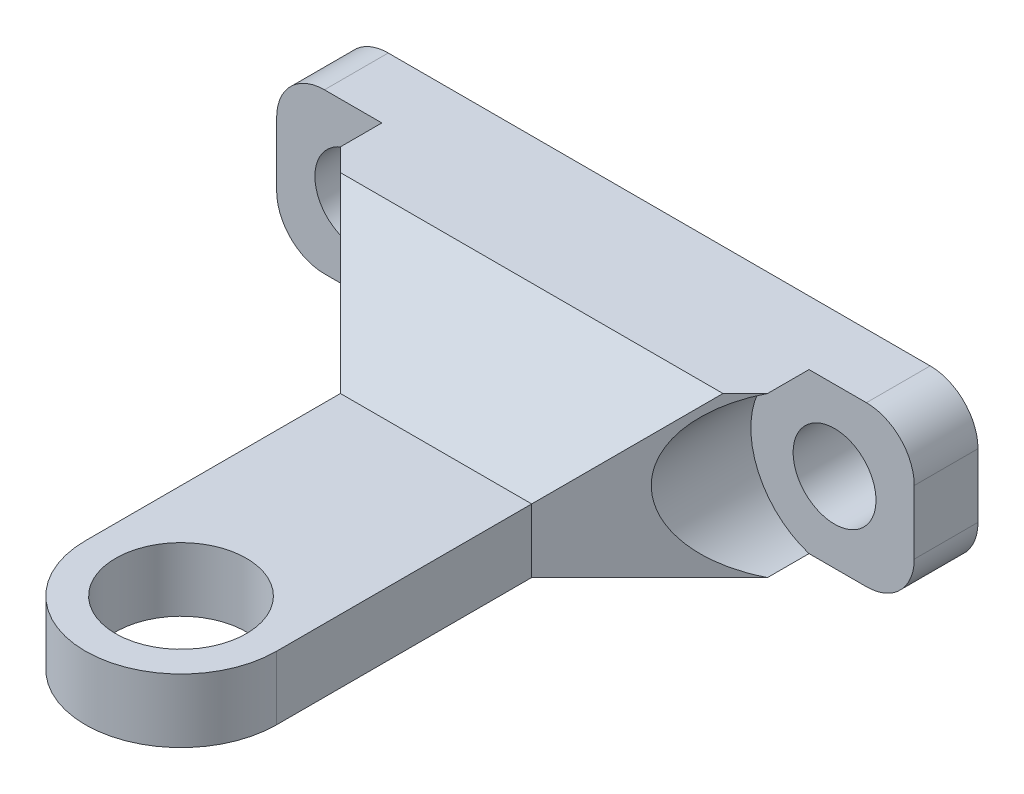
SolidWorks part; units mm, degrees
material "ABS"
ref_plane "Plano frontal" through (0, 0, 0) normal (0, 0, 1) x (1, 0, 0)
ref_plane "Plano superior" through (0, 0, 0) normal (0, 1, 0) x (1, 0, 0)
ref_plane "Plano direito" through (0, 0, 0) normal (1, 0, 0) x (0, 0, -1)
sketch "Esboço1" plane through (0, 0, 0) normal (0, 1, 0) x (1, 0, 0)
  line L0 (0, 18) -> (0, -18) construction
  line L1 (-20, 18) -> (20, 18)
  line L2 (-20, 18) -> (-20, -18)
  line L3 (-20, -18) -> (20, -18)
  line L4 (20, 18) -> (20, -18)
  line L5 (-20, 18) -> (20, -18) construction
  line L6 (-20, -18) -> (20, 18) construction
  line L7 (-6, -12) -> (-6, 14)
  line L8 (-20, 18) -> (20, 18)
  line L9 (-20, 18) -> (-20, 14)
  line L10 (-20, 14) -> (20, 14)
  line L11 (20, 18) -> (20, 14)
  line L12 (6, -12) -> (6, 14)
  circle A0 centre (0, -12) radius 6
  circle A1 centre (0, -12) radius 4.1
  point P0 (0, 0)
  dimension "D2" = 40
  dimension "D3" = 12
  dimension "D4" = 8.2
  dimension "D1" = 36
  dimension "D5" = 4
extrude "Ressalto-extrusão1" add sketch "Esboço1" along normal mid plane 4 contours L2 L10 L4 L1 | A0 L12 L10 L7 | A0 A1 region at (0, 0, -16) region at (0, 0, -3.3141) region at (-4.1226, 0, 16.1226)
sketch "Esboço2" plane through (0, 2, 0) normal (0, 1, 0) x (1, 0, 0)
  line L1 (-20, 18) -> (20, 18)
  line L2 (-20, 18) -> (-20, 14)
  line L3 (-20, 14) -> (20, 14)
  line L4 (20, 18) -> (20, 14)
extrude "Ressalto-extrusão2" add sketch "Esboço2" along normal blind 6
chamfer "Chanfro3" distance 10 angle 45 1 edges at (6, 0, -14)
chamfer "Chanfro4" distance 10 angle 45 1 edges at (-6, 0, -14)
chamfer "Chanfro5" distance 10 angle 45 1 edges at (0, 2, -14)
sketch "Esboço6" plane through (0, 0, -14) normal (0, 0, 1) x (1, 0, 0)
  line L0 (-20, 3) -> (20, 3) construction
  line L1 (-20, 8) -> (-20, -2) construction
  line L2 (20, 8) -> (20, -2) construction
  circle A0 centre (-15, 3) radius 2.6
  dimension "D1" = 5.2
  dimension "D2" = 5
extrude "Corte-extrusão2" cut sketch "Esboço6" along direction (0, 0, 1) on the side against the normal through all both and the other way through all
sketch "Esboço7" plane through (0, 0, -14) normal (0, 0, 1) x (1, 0, 0)
  circle A0 centre (-15, 3) radius 5.25
  dimension "D1" = 10.5
extrude "Corte-extrusão6" cut sketch "Esboço7" along normal through all
mirror "Espelhar2" about plane through (0, 0, 0) normal (1, 0, 0) of "Corte-extrusão6", "Corte-extrusão2"
fillet "Filete1" radius 3 4 edges at (20, -2, -16) (20, 8, -16) (-20, -2, -16) (-20, 8, -16)
